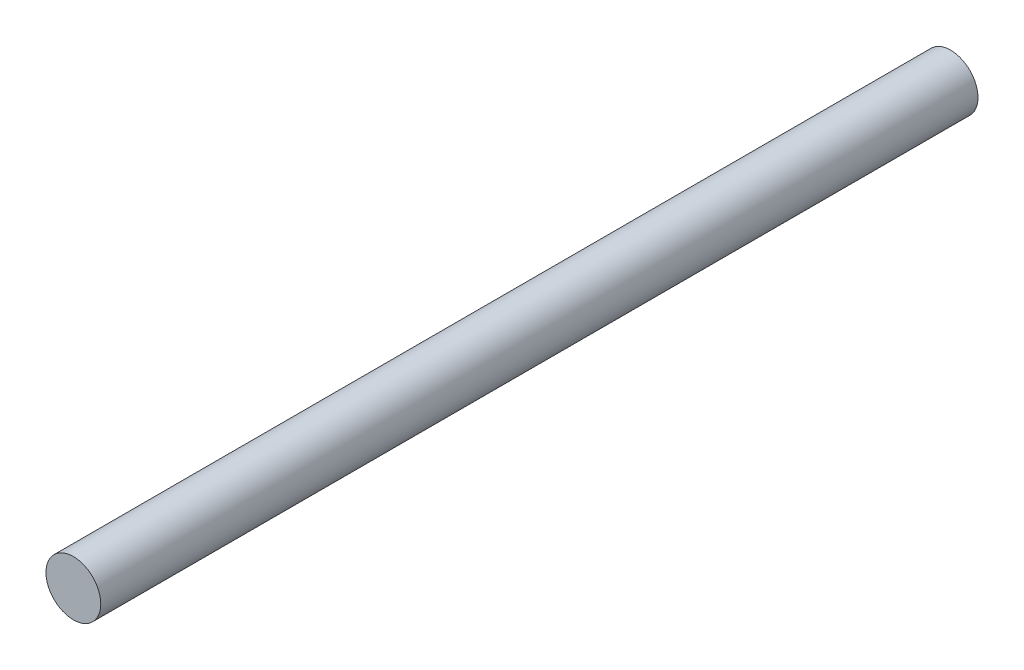
SolidWorks part; units mm, degrees
material "1.0037 (S235JR)"
ref_plane "Plan de face" through (0, 0, 0) normal (0, 0, 1) x (1, 0, 0)
ref_plane "Plan de dessus" through (0, 0, 0) normal (0, 1, 0) x (1, 0, 0)
ref_plane "Plan de droite" through (0, 0, 0) normal (1, 0, 0) x (0, 0, -1)
sketch "Esquisse1" plane through (0, 0, 0) normal (0, 0, 1) x (1, 0, 0)
  circle A0 centre (0, 0) radius 5
  dimension "D1" = 10
extrude "Boss.-Extru.1" add sketch "Esquisse1" along normal blind 70 and the other way blind 90
ref_axis "Axe1" through (0, 0, -82.5) along (0, 0, 1)
